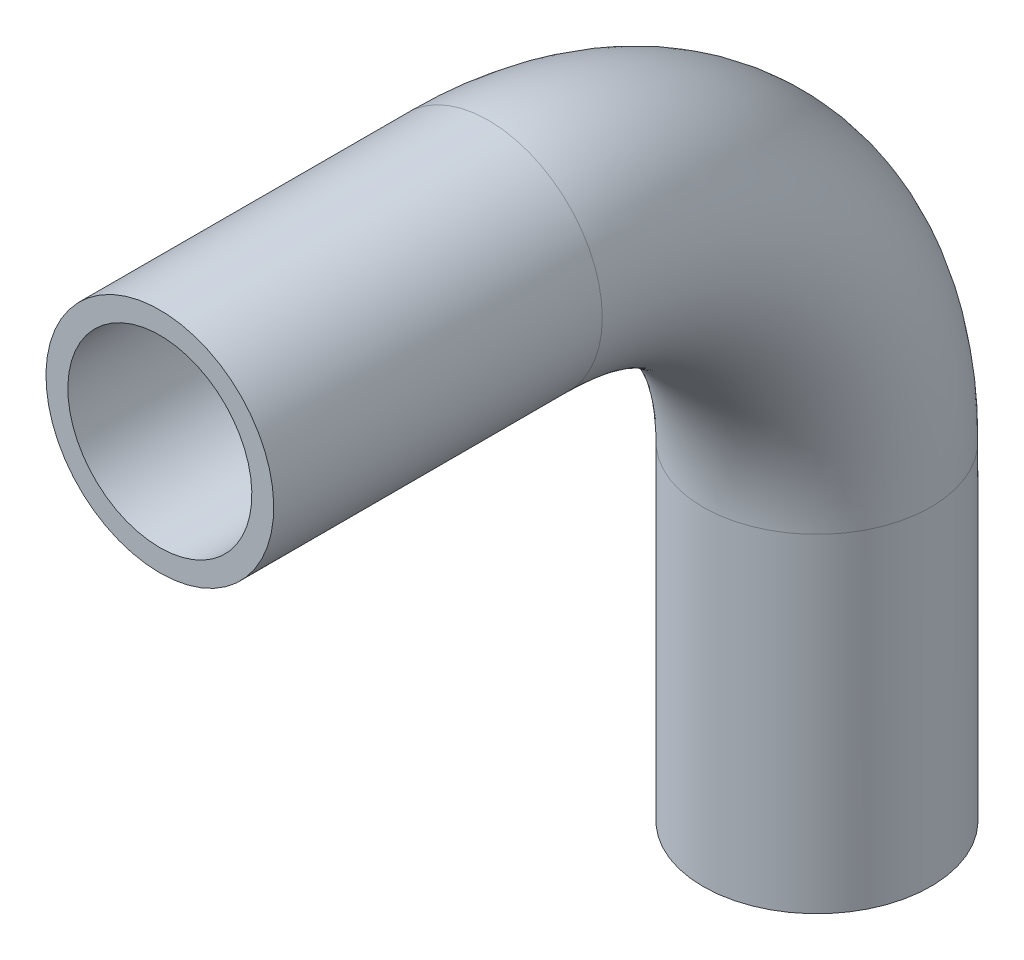
SolidWorks part; units mm, degrees
material "Chrome Stainless Steel"
ref_plane "Front" through (0, 0, 0) normal (0, 0, 1) x (1, 0, 0)
ref_plane "Top" through (0, 0, 0) normal (0, 1, 0) x (1, 0, 0)
ref_plane "Right" through (0, 0, 0) normal (1, 0, 0) x (0, 0, -1)
ref_axis "Axis1" through (0, 0, 55) along (0, 0, -1)
sketch "Sketch1" plane through (0, 0, 0) normal (1, 0, 0) x (0, 0, -1)
  line L0 (0, 0) -> (0, 19.05)
  line L1 (-19.05, 38.1) -> (-38.1, 38.1)
  arc A0 (0, 19.05) -> (-19.05, 38.1) centre (-19.05, 19.05) ccw
  point P6 (0, 38.1)
  dimension "D2" = 19.05
  dimension "D1" = 38.1
sketch "Sketch2" plane through (0, 0, 0) normal (0, 1, 0) x (1, 0, 0)
  circle A0 centre (0, 0) radius 6.604
  dimension "D1" = 13.208
sweep "Sweep-Thin1" add profiles "Sketch2" path "Sketch1" parameters "D1"=1.27
